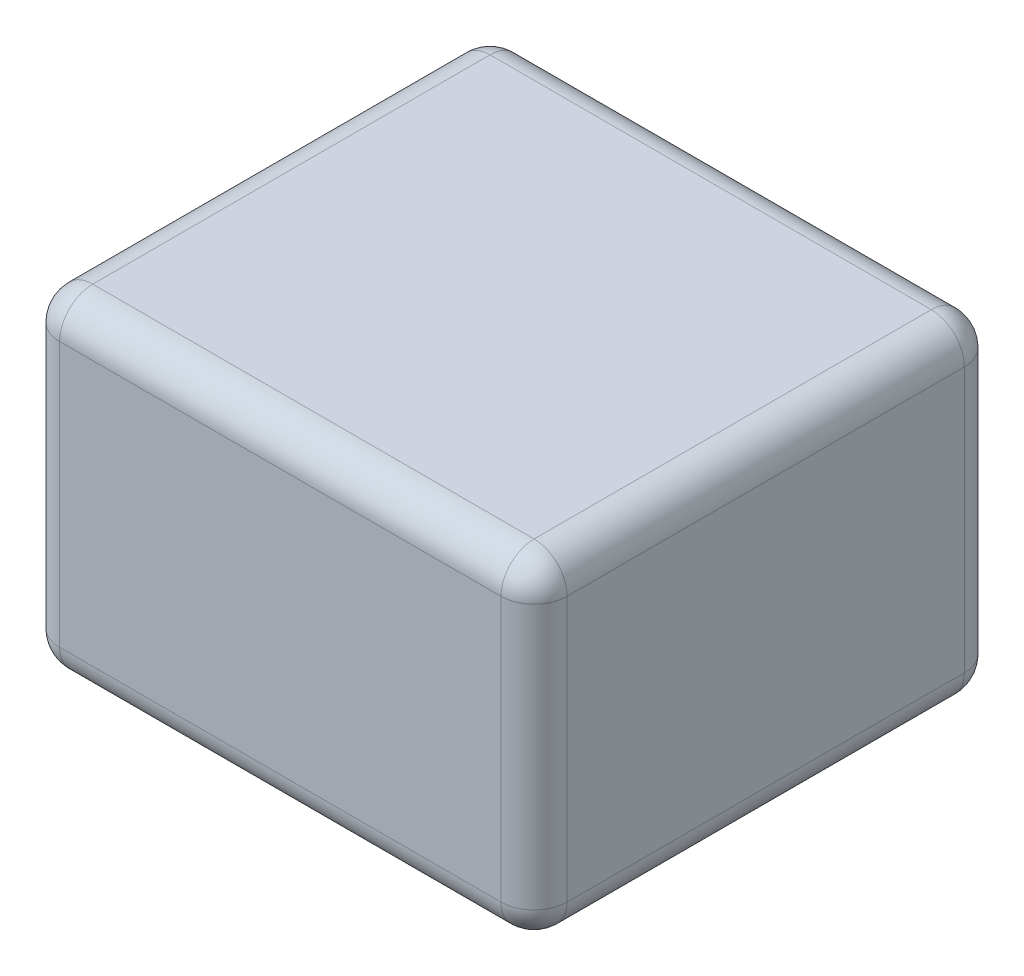
SolidWorks part; units mm, degrees
ref_plane "前视基准面" through (0, 0, 0) normal (0, 0, 1) x (1, 0, 0)
ref_plane "上视基准面" through (0, 0, 0) normal (0, 1, 0) x (1, 0, 0)
ref_plane "右视基准面" through (0, 0, 0) normal (1, 0, 0) x (0, 0, -1)
other "Configuration Table"
sketch "草图1" plane through (0, 0, 0) normal (0, 0, 1) x (1, 0, 0)
  line L1 (-23, -15) -> (23, -15)
  line L2 (-23, -15) -> (-23, 15)
  line L3 (-23, 15) -> (23, 15)
  line L4 (23, -15) -> (23, 15)
  line L5 (-23, -15) -> (23, 15) construction
  line L6 (-23, 15) -> (23, -15) construction
extrude "凸台-拉伸1" add sketch "草图1" along normal mid plane 42
fillet "圆角1" radius 3 12 edges at (23, 0, -21) (0, 15, -21) (-23, 0, -21) (0, -15, -21) (23, 0, 21) (0, 15, 21) (-23, 0, 21) (0, -15, 21) (23, -15, 0) (-23, -15, 0) (-23, 15, 0) (23, 15, 0) tangent propagation no
